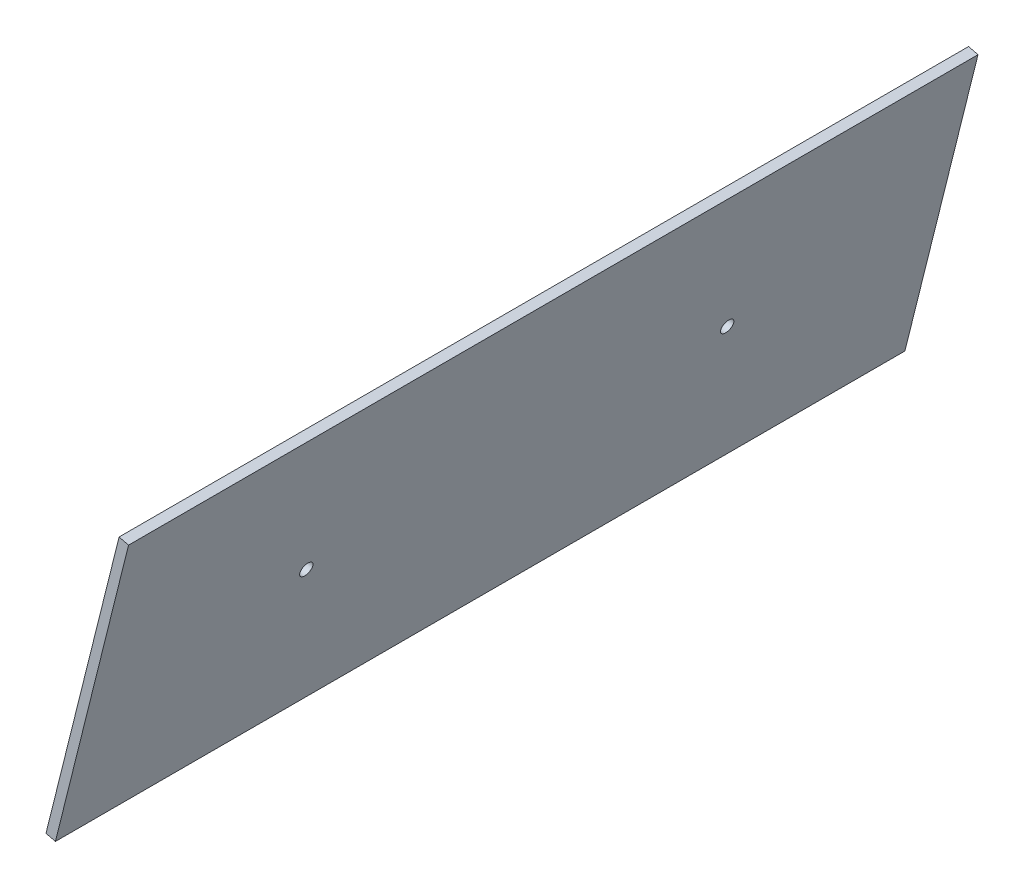
SolidWorks part; units mm, degrees
material "5052-H34"
ref_plane "Front Plane" through (0, 0, 0) normal (0, 0, 1) x (1, 0, 0)
ref_plane "Top Plane" through (0, 0, 0) normal (0, 1, 0) x (1, 0, 0)
ref_plane "Right Plane" through (0, 0, 0) normal (1, 0, 0) x (0, 0, -1)
sketch "Sketch1" plane through (0, 0, 0) normal (0, 0, 1) x (1, 0, 0)
  line L1 (-37.6295, -38.8249) -> (-13.7518, 56.9433)
  line L2 (-40.7102, -38.0568) -> (-16.8325, 57.7114)
  line L4 (-16.8325, 57.7114) -> (-13.7518, 56.9433)
  line L5 (-37.6295, -38.8249) -> (-40.7102, -38.0568)
  dimension "D2" = 98.7
  dimension "D3" = 3.175
extrude "Boss-Extrude1" add sketch "Sketch1" along normal blind 277.475 contours L1 L4 L2 L5
sketch "Sketch2" plane through (-26.3136, 6.5607, 0) normal (0.9703, -0.2419, 0) x (0, 0, -1)
  line L2 (-277.475, -46.775) -> (-277.475, 51.925) construction
  line L3 (0, -46.775) -> (0, 51.925) construction
  circle A0 centre (-207.475, 2.6168) radius 2.125
  circle A1 centre (-70, 2.6168) radius 2.125
  dimension "D1" = 4.25
  dimension "D2" = 4.25
  dimension "D3" = 70
  dimension "D4" = 70
extrude "Cut-Extrude1" cut sketch "Sketch2" against normal up to next
